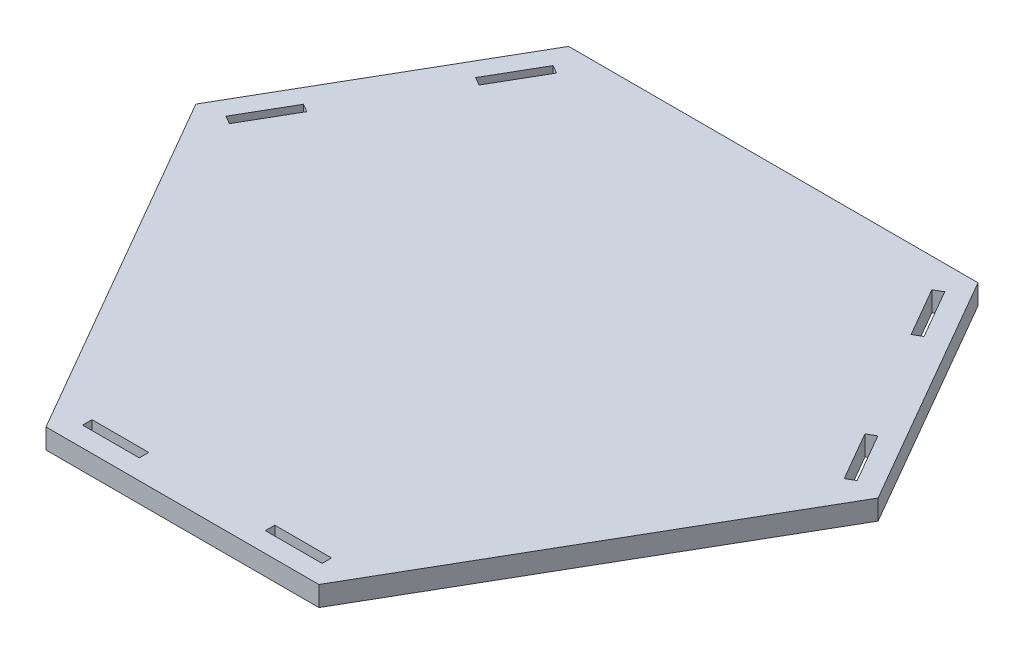
SolidWorks part; units mm, degrees
ref_plane "Front Plane" through (0, 0, 0) normal (0, 0, 1) x (1, 0, 0)
ref_plane "Top Plane" through (0, 0, 0) normal (0, 1, 0) x (1, 0, 0)
ref_plane "Right Plane" through (0, 0, 0) normal (1, 0, 0) x (0, 0, -1)
sketch "Sketch1" plane through (0, 0, 0) normal (0, 1, 0) x (1, 0, 0)
  line L0 (0, 200) -> (-173.2051, -100)
  line L1 (-173.2051, -100) -> (173.2051, -100)
  line L2 (173.2051, -100) -> (0, 200)
  line L4 (0, -175) -> (151.5544, 87.5)
  line L5 (151.5544, 87.5) -> (-151.5544, 87.5)
  line L6 (-151.5544, 87.5) -> (0, -175)
  circle A0 centre (0, 0) radius 200 construction
  circle A1 centre (0, 0) radius 100 construction
  circle A2 centre (0, 0) radius 175 construction
  circle A3 centre (0, 0) radius 87.5 construction
  dimension "D1" = 400
  dimension "D2" = 350
other "AlignGroup1"
extrude "Boss-Extrude1" add sketch "Sketch1" along normal blind 6.35 contours L0 L6 L1 L4 L2 L5 region at (0, 0, 0)
sketch "Sketch2" plane through (0, 6.35, 0) normal (0, 1, 0) x (1, 0, 0)
  line L0 (-43.3013, -100) -> (43.3013, -100) construction
  line L1 (-38, -90.7) -> (-20, -90.7)
  line L2 (-38, -90.7) -> (-38, -93.7)
  line L3 (-38, -93.7) -> (-20, -93.7)
  line L4 (-20, -90.7) -> (-20, -93.7)
  line L5 (0, -100) -> (0, 87.5) construction
  line L6 (64.9519, 87.5) -> (-64.9519, 87.5) construction
  line L7 (38, -90.7) -> (38, -93.7)
  line L8 (-86.6025, 50) -> (75.7772, -43.75) construction
  line L9 (-62.1466, 79.759) -> (-59.5485, 78.259)
  line L10 (20, -90.7) -> (20, -93.7)
  line L11 (-62.1466, 79.759) -> (-71.1466, 64.1705)
  line L12 (-71.1466, 64.1705) -> (-68.5485, 62.6705)
  line L13 (38, -93.7) -> (20, -93.7)
  line L14 (38, -90.7) -> (20, -90.7)
  line L15 (-59.5485, 78.259) -> (-68.5485, 62.6705)
  line L16 (-64.9519, 87.5) -> (-108.2532, 12.5) construction
  line L17 (43.3013, -100) -> (108.2532, 12.5) construction
  line L18 (-97.5485, 12.441) -> (-88.5485, 28.0295)
  line L19 (-91.1466, 29.5295) -> (-88.5485, 28.0295)
  line L20 (-100.1466, 13.941) -> (-91.1466, 29.5295)
  line L21 (-100.1466, 13.941) -> (-97.5485, 12.441)
  line L22 (86.6025, 50) -> (-75.7772, -43.75) construction
  line L23 (108.2532, 12.5) -> (64.9519, 87.5) construction
  line L24 (-108.2532, 12.5) -> (-43.3013, -100) construction
  line L25 (100.1466, 13.941) -> (91.1466, 29.5295)
  line L26 (59.5485, 78.259) -> (62.1466, 79.759)
  line L27 (59.5485, 78.259) -> (68.5485, 62.6705)
  line L28 (68.5485, 62.6705) -> (71.1466, 64.1705)
  line L29 (62.1466, 79.759) -> (71.1466, 64.1705)
  line L30 (88.5485, 28.0295) -> (91.1466, 29.5295)
  line L31 (97.5485, 12.441) -> (88.5485, 28.0295)
  line L32 (97.5485, 12.441) -> (100.1466, 13.941)
  point P4 (-29, -93.7)
  dimension "D1" = 18
  dimension "D2" = 3
  dimension "D3" = 6.3
  dimension "D4" = 38
  dimension "D5" = 6.3
  dimension "D6" = 18
  dimension "D7" = 3
  dimension "D8" = 38
  dimension "D9" = 18
  dimension "D10" = 3
  dimension "D11" = 38
  dimension "D12" = 6.3
extrude "Cut-Extrude1" cut sketch "Sketch2" against normal through all
sketch "Sketch3" plane through (0, 6.35, 0) normal (0, 1, 0) x (1, 0, 0)
  point P0 (0, 0)
ref_axis "Axis1" through (0, 0, 0) along (0, 1, 0)
